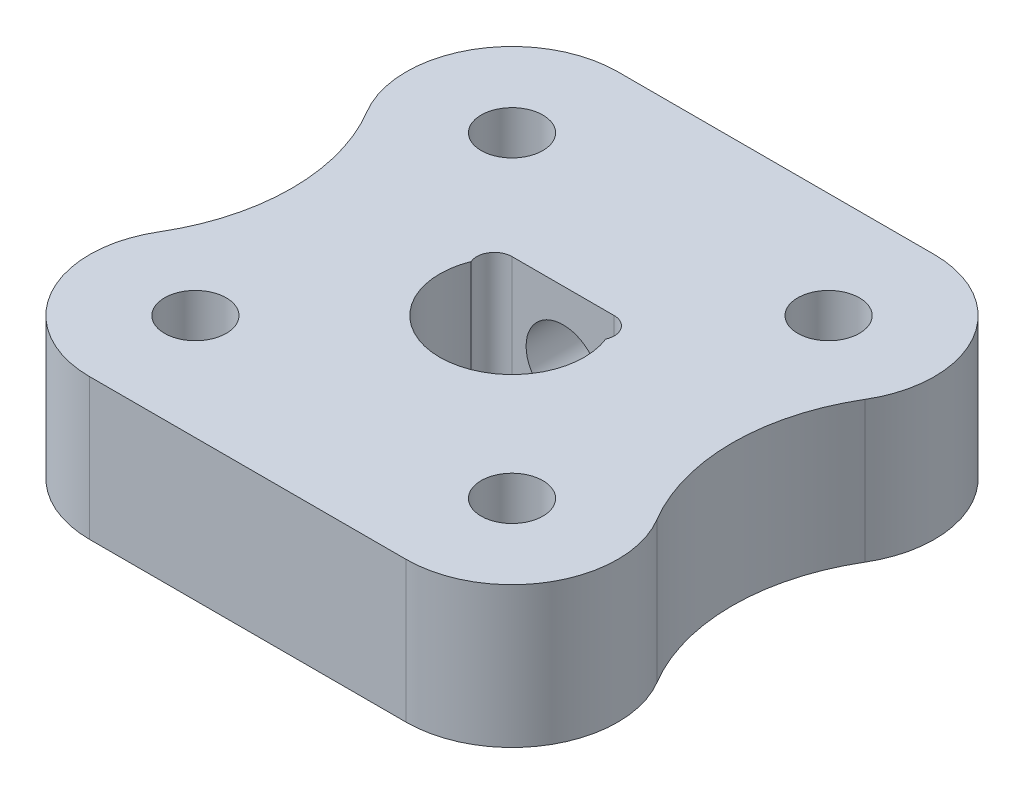
SolidWorks part; units mm, degrees
ref_plane "Front Plane" through (0, 0, 0) normal (0, 0, 1) x (1, 0, 0)
ref_plane "Top Plane" through (0, 0, 0) normal (0, 1, 0) x (1, 0, 0)
ref_plane "Right Plane" through (0, 0, 0) normal (1, 0, 0) x (0, 0, -1)
sketch "Sketch1" plane through (0, 0, 0) normal (0, 1, 0) x (1, 0, 0)
  line L0 (-9.35, 0) -> (9.35, 0) construction
  line L1 (0, 9.35) -> (0, -9.35) construction
  line L2 (0, 0) -> (6.6114, 6.6114) construction
  line L3 (-1.4491, 1.45) -> (1.4491, 1.45)
  line L4 (-1.4491, 1.45) -> (-1.4491, 0) construction
  line L5 (-4.4901, 7.4901) -> (4.4901, 7.4901)
  line L7 (-6.25, 0) -> (-6.25, -2.0605) construction
  line L8 (-4.4901, -7.4901) -> (4.4901, -7.4901)
  circle A0 centre (0, 0) radius 9.35
  circle A1 centre (0, 0) radius 2.05
  circle A2 centre (4.4901, 4.4901) radius 0.875
  circle A3 centre (-4.4901, 4.4901) radius 0.875
  circle A4 centre (4.4901, -4.4901) radius 0.875
  circle A5 centre (-4.4901, -4.4901) radius 0.875
  circle A6 centre (-1.4491, 0.95) radius 0.5
  circle A7 centre (1.4491, 0.95) radius 0.5
  circle A8 centre (-7.5, 0) radius 1.25
  circle A9 centre (-4.4901, 4.4901) radius 3
  circle A10 centre (-4.4901, -4.4901) radius 3
  arc A11 (-7.0649, -2.9504) -> (-7.0649, 2.9504) centre (-11.9988, 0) ccw
  arc A12 (7.0649, -2.9504) -> (7.0649, 2.9504) centre (11.9988, 0) cw
  circle A13 centre (4.4901, -4.4901) radius 3
  circle A14 centre (4.4901, 4.4901) radius 3
  point P19 (0, -2.05)
  dimension "D2" = 4.1
  dimension "D3" = 1.75
  dimension "D7" = 1
  dimension "D9" = 2.5
  dimension "D11" = 6
  dimension "D4" = 6.35
  dimension "D5" = 45
  dimension "D6" = 3.5
  dimension "D10" = 15
extrude "Base shape" add sketch "Sketch1" along normal blind 4 contours A12 A14 A0 A9 A11 A10 A13 A1 A7 A6 | A9 A3 | A14 A2 | A13 A4 | A10 A5 | L3 A1 region at (0, 0, -1.6933) region at (0, 0, -7.2842) region at (-2.4288, 0, -6.5514) region at (5.6057, 0, -7.1834) region at (-7.3832, 0, 4.8484) region at (7.3001, 0, 3.714)
sketch "Sketch3" plane through (0, 0, -7.4901) normal (0, 0, 1) x (1, 0, 0)
  line L0 (-4.4901, 4) -> (4.4901, 0) construction
  circle A0 centre (0, 2) radius 1.05
  point P2 (0, 2)
  point P3 (-4.4901, 4)
  point P4 (4.4901, 0)
  dimension "D1" = 2.1
extrude "M2.5 Grub screw cut" cut sketch "Sketch3" along normal up to next
sketch "Main CS" plane through (0, 4, 0) normal (0, 1, 0) x (1, 0, 0)
  line L1 (-7.4901, 7.4901) -> (7.4901, 7.4901)
  line L2 (-7.4901, 7.4901) -> (-7.4901, -7.4901)
  line L3 (-7.4901, -7.4901) -> (7.4901, -7.4901)
  line L4 (7.4901, 7.4901) -> (7.4901, -7.4901)
  line L5 (-7.4901, 7.4901) -> (7.4901, -7.4901) construction
  line L6 (-7.4901, -7.4901) -> (7.4901, 7.4901) construction
  line L7 (-4.4901, -7.4901) -> (4.4901, -7.4901) construction
  arc A0 (-4.4901, 7.4901) -> (-7.0649, 2.9504) centre (-4.4901, 4.4901) ccw construction
  point P0 (0, 0)
  point P9 (0, 0)
  point P10 (7.4901, -7.4901)
sketch "Grub CS" plane through (0, 0, -7.4901) normal (0, 0, -1) x (-1, 0, 0)
  line L0 (-4.4901, 4) -> (4.4901, 0) construction
  line L1 (0, 2) -> (4.4901, 2) construction
  line L2 (4.4901, 4) -> (4.4901, 0) construction
  line L3 (0, 2) -> (0, 4) construction
  line L4 (4.4901, 4) -> (-4.4901, 4) construction
  point P4 (0, 2)
  point P10 (0, 0)
